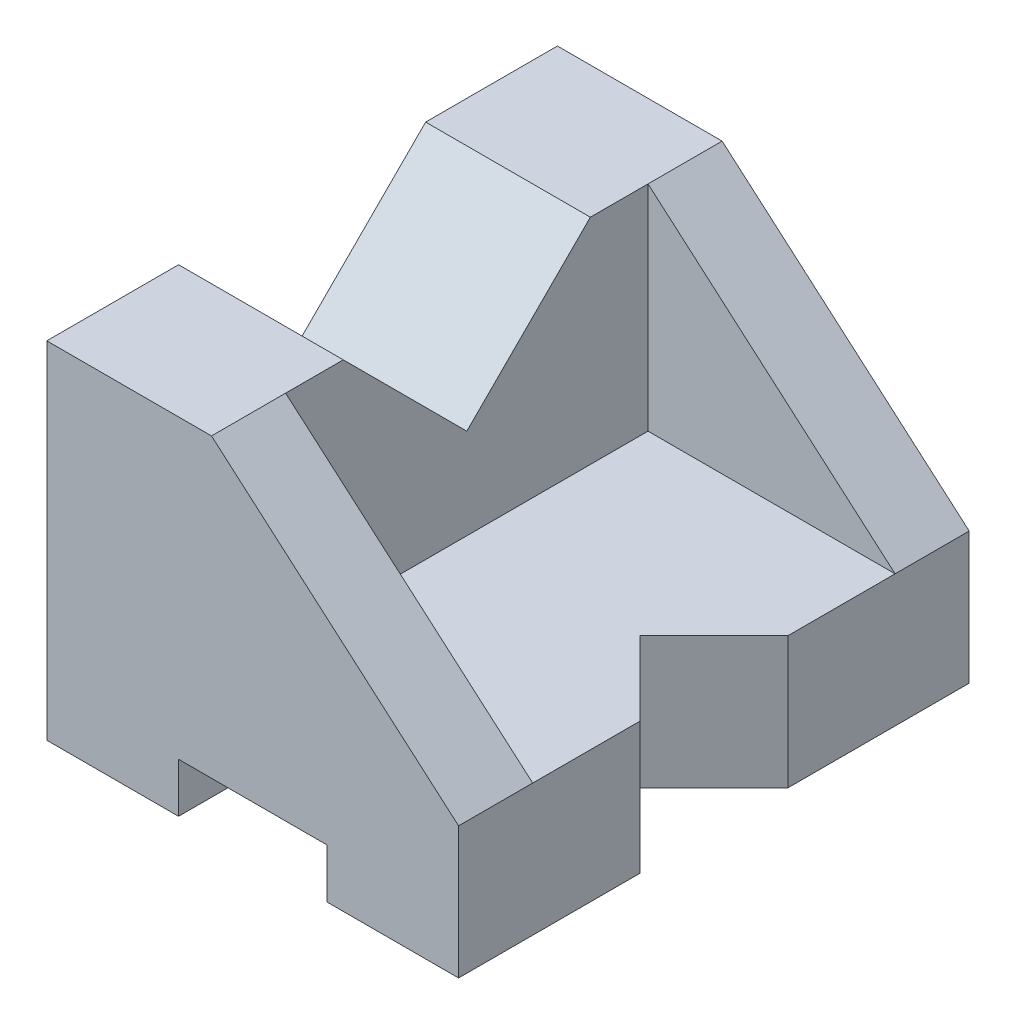
SolidWorks part; units mm, degrees
ref_plane "Front Plane" through (0, 0, 0) normal (0, 0, 1) x (1, 0, 0)
ref_plane "Top Plane" through (0, 0, 0) normal (0, 1, 0) x (1, 0, 0)
ref_plane "Right Plane" through (0, 0, 0) normal (1, 0, 0) x (0, 0, -1)
sketch "Sketch1" plane through (0, 0, 0) normal (0, 0, 1) x (1, 0, 0)
  line L0 (-25, -6) -> (-9, -6)
  line L1 (-9, -6) -> (-9, 0)
  line L2 (-9, 0) -> (9, 0)
  line L3 (9, 0) -> (9, -6)
  line L4 (9, -6) -> (25, -6)
  line L5 (25, -6) -> (25, 10)
  line L6 (25, 10) -> (-5, 36)
  line L7 (-5, 36) -> (-25, 36)
  line L8 (-25, 36) -> (-25, -6)
  line L9 (-5, 36) -> (-5, 10)
  line L10 (-5, 10) -> (25, 10)
  point P9 (0, 0)
  dimension "D1" = 42
  dimension "D2" = 16
  dimension "D3" = 16
  dimension "D4" = 20
  dimension "D5" = 6
  dimension "D6" = 50
extrude "Boss-Extrude1" add sketch "Sketch1" along normal mid plane 62 contours L10 L9 L7 L8 L0 L1 L2 L3 L4 L5 region at (-6.4356, 11.4554, 0)
extrude "Boss-Extrude2" add sketch "Sketch1<3>" along normal blind 9 from offset 22 contours L9 L10 L6 region at (5, 18.6667, 0)
sketch "Sketch1<3>" plane through (0, 0, 0) normal (0, 0, 1) x (1, 0, 0) same geometry as "Sketch1"
extrude "Boss-Extrude3" add sketch "Sketch1<4>" against normal blind 9 from offset 22 contours L9 L10 L6 region at (5, 18.6667, 0) offset against normal yes
sketch "Sketch1<4>" plane through (0, 0, 0) normal (0, 0, 1) x (1, 0, 0) same geometry as "Sketch1"
sketch "Sketch2" plane through (-5, 0, 0) normal (1, 0, 0) x (0, 0, -1)
  line L0 (-15, 36) -> (0, 21)
  line L1 (-22, 36) -> (22, 36) construction
  line L2 (0, 21) -> (15, 36)
  point P5 (0, 0)
  dimension "D1" = 16
  dimension "D2" = 30
  dimension "D3" = 15
extrude "Cut-Extrude1" cut sketch "Sketch2" against normal through all and the other way through all
sketch "Sketch3" plane through (0, 10, 0) normal (0, 1, 0) x (1, 0, 0)
  line L0 (25, 9) -> (16, 0)
  line L1 (25, -22) -> (25, 22) construction
  line L2 (16, 0) -> (25, -9)
  point P5 (0, 0)
  dimension "D1" = 22
  dimension "D2" = 18
  dimension "D3" = 9
extrude "Cut-Extrude2" cut sketch "Sketch3" against normal through all and the other way through all
